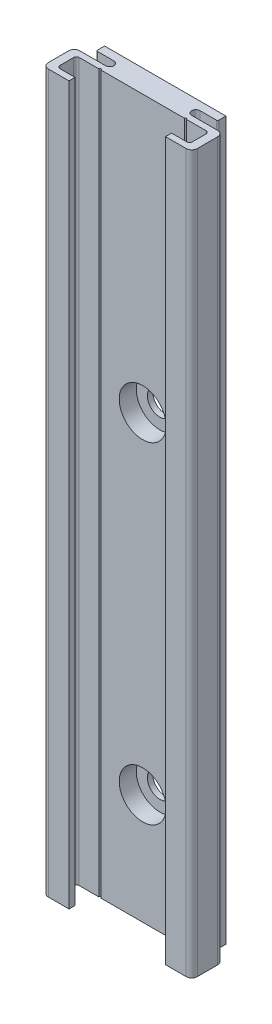
SolidWorks part; units mm, degrees
ref_plane "Plan de face" through (0, 0, 0) normal (0, 0, 1) x (1, 0, 0)
ref_plane "Plan de dessus" through (0, 0, 0) normal (0, 1, 0) x (1, 0, 0)
ref_plane "Plan de droite" through (0, 0, 0) normal (1, 0, 0) x (0, 0, -1)
ref_plane "Plan1" through (0, 0, 0) normal (0, -1, 0) x (1, 0, 0)
sketch "Esquisse1" plane through (0, 0, 0) normal (0, -1, 0) x (1, 0, 0)
  line L0 (13.5, 8.7) -> (-13.5, 8.7)
  line L1 (-13.5, 8.7) -> (-13.5, 3)
  line L2 (-13.5, 3) -> (-7.8, 3)
  line L3 (-7.8, 1.5) -> (-11, 1.5)
  line L4 (-11, 1.5) -> (-11, 0)
  line L5 (-11, 0) -> (11, 0)
  line L6 (11, 0) -> (11, 1.5)
  line L7 (11, 1.5) -> (7.8, 1.5)
  line L8 (7.8, 3) -> (13.5, 3)
  line L9 (13.5, 3) -> (13.5, 8.7)
  arc A0 (-7.8, 3) -> (-7.8, 1.5) centre (-7.8, 2.25) cw
  arc A1 (7.8, 1.5) -> (7.8, 3) centre (7.8, 2.25) cw
extrude "Boss.-Extru.1" add sketch "Esquisse1" against normal blind 1000
sketch "Esquisse2" plane through (0, 1000, 0) normal (0, 1, 0) x (-1, 0, 0)
  line L0 (8.75, 8.7) -> (-8.75, 8.7)
  line L1 (-8.75, 8.7) -> (-8.75, 7.6)
  line L2 (-8.75, 7.6) -> (-12, 7.6)
  line L3 (-12, 7.6) -> (-12, 4.1)
  line L4 (-12, 4.1) -> (12, 4.1)
  line L5 (12, 4.1) -> (12, 7.6)
  line L6 (12, 7.6) -> (8.75, 7.6)
  line L7 (8.75, 7.6) -> (8.75, 8.7)
extrude "Enlèv. mat.-Extru.1" cut sketch "Esquisse2" against normal through all
hole_wizard "Chambrage pour vis à tête hexagonale M41" positions "Esquisse4" profile "Esquisse3" counterbore size "M4" standard "Ansi Metric"
sketch "Esquisse4" plane through (0, 0, 4.1) normal (0, 0, 1) x (1, 0, 0)
  point P0 (0, 980)
  point P1 (0, 920)
  point P2 (0, 860)
  point P3 (0, 800)
  point P4 (0, 740)
  point P5 (0, 680)
  point P6 (0, 620)
  point P7 (0, 560)
  point P8 (0, 500)
  point P9 (0, 440)
  point P10 (0, 380)
  point P11 (0, 320)
  point P12 (0, 260)
  point P13 (0, 200)
  point P14 (0, 140)
  point P15 (0, 80)
  point P16 (0, 20)
sketch "Esquisse3" plane through (0, 980, 4.1) normal (1, 0, 0) x (0, -1, 0)
  line L0 (0, 0) -> (0, 4.1)
  line L1 (0, 4.1) -> (2.25, 4.1)
  line L3 (2.25, 4.1) -> (2.25, 3.1)
  line L4 (2.25, 3.1) -> (4.25, 3.1)
  line L5 (4.25, 3.1) -> (4.25, 0)
  line L7 (4.25, 0) -> (0, 0)
  line L11 (0, -6.35) -> (0, 107.95) construction
  dimension "Diamètre du perçage jusqu'au prochain" = 4.5
  dimension "Profondeur du perçage jusqu'au prochain" = 4.1
  dimension "Diamètre du chambrage" = 8.5
  dimension "Profondeur du chambrage" = 3.1
hole_wizard "Diamètre du perçage Ø0.4 (0.4)1" positions "Esquisse6" profile "Esquisse5" hole size "Ø0.4" standard "Ansi Metric"
sketch "Esquisse6" plane through (0, 0, 0) normal (0, -1, 0) x (-1, 0, 0)
  point P0 (7.75, -4.1)
  point P1 (-7.75, -4.1)
sketch "Esquisse5" plane through (-7.75, 0, 4.1) normal (1, 0, 0) x (0, 0, -1)
  line L0 (0, 0) -> (0, 1000)
  line L1 (0, 1000) -> (0.2, 1000)
  line L2 (0.2, 1000) -> (0.2, 0)
  line L5 (0.2, 0) -> (0, 0)
  line L11 (0, -6.35) -> (0, 107.95) construction
  dimension "Diamètre du perçage jusqu'au prochain" = 0.4
  dimension "Profondeur du perçage jusqu'au prochain" = 1000
fillet "Congé1" radius 0.2 2 edges at (11, 500, 1.5) (-11, 500, 1.5) tangent propagation no
fillet "Congé2" radius 0.5 4 edges at (12, 500, 7.6) (12, 500, 4.1) (-12, 500, 7.6) (-12, 500, 4.1) tangent propagation no
fillet "Congé3" radius 1 4 edges at (13.5, 500, 3) (13.5, 500, 8.7) (-13.5, 500, 3) (-13.5, 500, 8.7) tangent propagation no
sketch "Esquisse9" plane through (0, 0, 0) normal (0, 0, 1) x (1, 0, 0)
  line L0 (-13.5, 0) -> (-13.5, 1000) construction
  line L1 (-13.5, 130) -> (13.5, 130)
  line L2 (-13.5, 130) -> (-13.5, 1000)
  line L3 (-13.5, 1000) -> (13.5, 1000)
  line L4 (13.5, 130) -> (13.5, 1000)
  line L5 (13.5, 1000) -> (13.5, 0) construction
  line L6 (7.55, 1000) -> (-7.55, 1000) construction
  dimension "D1" = 130
extrude "Enlèv. mat.-Extru.2" cut sketch "Esquisse9" against normal through all both and the other way through all
